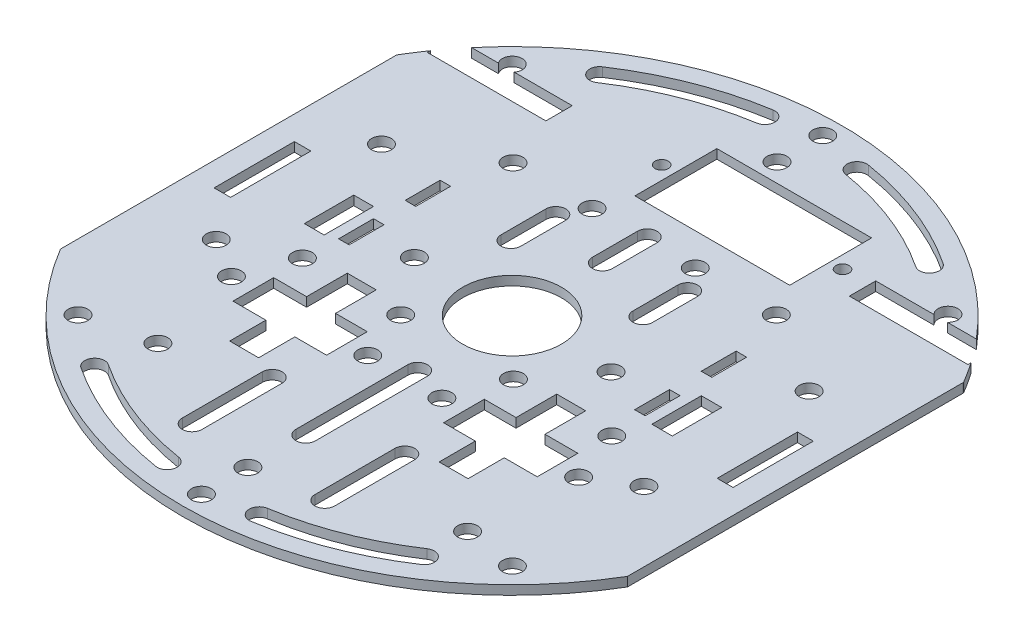
SolidWorks part; units mm, degrees
ref_plane "Plan de face" through (0, 0, 0) normal (0, 0, 1) x (1, 0, 0)
ref_plane "Plan de dessus" through (0, 0, 0) normal (0, 1, 0) x (1, 0, 0)
ref_plane "Plan de droite" through (0, 0, 0) normal (1, 0, 0) x (0, 0, -1)
sketch "Esquisse1" plane through (0, 0, 0) normal (0, 1, 0) x (1, 0, 0)
  line L0 (230, 494) -> (1150, 494) construction
  line L1 (230, 494) -> (1150, 494) construction
  line L2 (1049.7748, 1753.5) -> (2703.7748, 1753.5) construction
  line L3 (35.8344, 116.4831) -> (35.8344, 167.52)
  line L4 (121.9144, 167.4519) -> (121.9144, 116.5513)
  line L5 (88.9323, 158.6153) -> (88.9323, 151.8005) construction
  line L6 (121.9144, 116.5513) -> (121.9144, 116.4831)
  line L7 (55.7773, 128.9032) -> (60.7773, 128.9032)
  line L8 (55.7773, 128.9032) -> (55.7773, 122.7236)
  line L9 (55.7773, 122.7236) -> (60.7773, 122.7236)
  line L10 (60.7773, 122.7236) -> (60.7773, 117.2265)
  line L11 (60.7773, 117.2265) -> (65.1744, 117.2265)
  line L12 (65.1744, 117.2265) -> (65.1744, 122.7236)
  line L13 (65.1744, 122.7236) -> (69.9925, 122.7236)
  line L14 (69.9925, 122.7236) -> (69.9925, 128.9032)
  line L15 (69.9925, 128.9032) -> (65.1744, 128.9032)
  line L16 (65.1744, 128.9032) -> (65.1744, 135.081)
  line L17 (65.1744, 135.081) -> (60.7773, 135.081)
  line L18 (60.7773, 135.081) -> (60.7773, 128.9032)
  line L19 (68.9056, 158.6153) -> (68.9056, 151.8005) construction
  line L20 (70.4056, 158.6153) -> (70.4056, 151.8005)
  line L21 (67.4056, 158.6153) -> (67.4056, 151.8005)
  line L22 (78.7942, 162.6149) -> (78.7942, 155.8001) construction
  line L23 (80.2942, 162.6149) -> (80.2942, 155.8001)
  line L24 (77.2942, 162.6149) -> (77.2942, 155.8001)
  line L25 (68.7987, 115.6611) -> (68.7987, 103.5071) construction
  line L26 (70.2987, 115.6611) -> (70.2987, 103.5071)
  line L27 (67.2987, 115.6611) -> (67.2987, 103.5071)
  line L28 (39.458, 148.3706) -> (41.958, 148.3706)
  line L29 (41.958, 148.3706) -> (41.958, 136.1826)
  line L30 (41.958, 136.1826) -> (39.458, 136.1826)
  line L31 (39.458, 136.1826) -> (39.458, 148.3706)
  line L32 (55.6035, 149.0513) -> (57.2035, 149.0513)
  line L33 (54.0029, 138.3405) -> (51.0029, 138.3405)
  line L34 (54.0029, 138.3405) -> (54.0029, 145.8405)
  line L35 (54.0029, 145.8405) -> (51.0029, 145.8405)
  line L36 (51.0029, 138.3405) -> (51.0029, 145.8405)
  line L37 (55.6035, 138.9387) -> (57.2035, 138.9387)
  line L38 (55.6035, 138.9387) -> (55.6035, 144.2387)
  line L39 (55.6035, 144.2387) -> (57.2035, 144.2387)
  line L40 (57.2035, 138.9387) -> (57.2035, 144.2387)
  line L41 (55.6035, 149.0513) -> (55.6035, 154.3513)
  line L42 (55.6035, 154.3513) -> (57.2035, 154.3513)
  line L43 (57.2035, 149.0513) -> (57.2035, 154.3513)
  line L44 (35.8344, 142.0016) -> (121.9144, 142.0016) construction
  line L45 (78.8744, 142.0016) -> (78.8744, 76.4199) construction
  line L46 (78.9075, 127.6391) -> (78.9075, 110.6391) construction
  line L47 (80.4075, 127.6391) -> (80.4075, 110.6391)
  line L48 (77.4075, 127.6391) -> (77.4075, 110.6391)
  line L49 (35.8344, 162.6149) -> (121.9144, 162.6149) construction
  line L50 (87.4323, 158.6153) -> (87.4323, 151.8005)
  line L51 (90.4323, 158.6153) -> (90.4323, 151.8005)
  line L52 (88.9323, 115.6611) -> (88.9323, 103.5071) construction
  line L53 (87.4323, 115.6611) -> (87.4323, 103.5071)
  line L54 (90.4323, 115.6611) -> (90.4323, 103.5071)
  line L55 (100.5453, 149.0513) -> (100.5453, 154.3513)
  line L56 (102.1454, 154.3551) -> (100.5453, 154.3513)
  line L57 (102.1454, 149.0551) -> (102.1454, 154.3551)
  line L58 (100.5454, 138.9387) -> (100.5454, 144.2387)
  line L59 (102.1454, 144.2387) -> (100.5454, 144.2387)
  line L60 (102.1454, 138.9387) -> (102.1454, 144.2387)
  line L61 (102.1454, 138.9387) -> (100.5454, 138.9387)
  line L62 (106.8661, 138.3405) -> (106.8661, 145.8405)
  line L63 (103.7673, 145.8405) -> (106.8661, 145.8405)
  line L64 (103.7673, 138.3405) -> (103.7673, 145.8405)
  line L65 (103.7673, 138.3405) -> (106.8661, 138.3405)
  line L66 (102.1454, 149.0551) -> (100.5453, 149.0513)
  line L67 (118.245, 136.1826) -> (118.245, 148.3706)
  line L68 (115.8366, 136.1826) -> (118.245, 136.1826)
  line L69 (115.8366, 148.3706) -> (115.8366, 136.1826)
  line L70 (118.245, 148.3706) -> (115.8366, 148.3706)
  line L71 (96.9716, 135.081) -> (96.9716, 128.9032)
  line L72 (92.5745, 135.081) -> (96.9716, 135.081)
  line L73 (92.5745, 128.9032) -> (92.5745, 135.081)
  line L74 (87.7564, 128.9032) -> (92.5745, 128.9032)
  line L75 (87.7564, 122.7236) -> (87.7564, 128.9032)
  line L76 (92.5745, 122.7236) -> (87.7564, 122.7236)
  line L77 (92.5745, 117.2265) -> (92.5745, 122.7236)
  line L78 (96.9716, 117.2265) -> (92.5745, 117.2265)
  line L79 (96.9716, 122.7236) -> (96.9716, 117.2265)
  line L80 (101.9716, 122.7236) -> (96.9716, 122.7236)
  line L81 (101.9716, 128.9032) -> (101.9716, 122.7236)
  line L82 (101.9716, 128.9032) -> (96.9716, 128.9032)
  line L84 (72.4514, 167.0754) -> (95.9525, 167.0754)
  line L85 (72.4514, 167.0754) -> (72.4514, 179.5181)
  line L86 (72.4514, 179.5181) -> (95.9525, 179.5181)
  line L87 (95.9525, 167.0754) -> (95.9525, 179.5181)
  arc A1 (35.8344, 116.4831) -> (121.9144, 116.4831) centre (78.8744, 142.0016) ccw
  circle A2 centre (78.8744, 142.0016) radius 7.5
  arc A3 (121.8796, 167.5788) -> (35.8344, 167.52) centre (78.8744, 142.0016) ccw
  circle A4 centre (55.6386, 111.4684) radius 1.5
  circle A5 centre (52.4216, 125.8435) radius 1.5
  circle A6 centre (46.4093, 129.5605) radius 1.5
  circle A7 centre (45.8266, 109.1504) radius 1.5
  circle A9 centre (55.394, 133.6521) radius 1.5
  circle A10 centre (63.822, 142.2216) radius 1.5
  circle A11 centre (70.318, 133.6521) radius 1.5
  circle A12 centre (73.1582, 125.8134) radius 1.5
  circle A14 centre (78.7794, 94.9342) radius 1.5
  circle A15 centre (58.8593, 162.1633) radius 1.5
  circle A16 centre (78.7794, 101.9917) radius 1.5
  circle A17 centre (45.8266, 175.0806) radius 1.5
  circle A18 centre (78.7794, 182.3243) radius 1.5
  circle A19 centre (46.4093, 154.6416) radius 1.5
  circle A20 centre (78.7794, 189.2658) radius 1.5
  circle A21 centre (70.8644, 162.1633) radius 1.5
  arc A24 (70.4056, 158.6153) -> (67.4056, 158.6153) centre (68.9056, 158.6153) ccw
  arc A25 (67.4056, 151.8005) -> (70.4056, 151.8005) centre (68.9056, 151.8005) ccw
  arc A26 (80.2942, 162.6149) -> (77.2942, 162.6149) centre (78.7942, 162.6149) ccw
  arc A27 (77.2942, 155.8001) -> (80.2942, 155.8001) centre (78.7942, 155.8001) ccw
  arc A30 (70.2987, 115.6611) -> (67.2987, 115.6611) centre (68.7987, 115.6611) ccw
  arc A31 (67.2987, 103.5071) -> (70.2987, 103.5071) centre (68.7987, 103.5071) ccw
  arc A35 (53.8408, 103.6654) -> (71.8854, 96.6187) centre (79.1758, 141.9141) ccw construction
  arc A36 (53.0125, 102.4148) -> (71.647, 95.1377) centre (79.1758, 141.9141) ccw
  arc A37 (54.6692, 104.9159) -> (72.1238, 98.0996) centre (79.1758, 141.9141) ccw
  arc A38 (54.6692, 104.9159) -> (53.0125, 102.4148) centre (53.8408, 103.6654) ccw
  arc A39 (71.647, 95.1377) -> (72.1238, 98.0996) centre (71.8854, 96.6187) ccw
  circle A40 centre (78.9075, 110.6391) radius 1.5
  circle A41 centre (78.9075, 127.6391) radius 1.5
  arc A42 (80.4075, 127.6391) -> (77.4075, 127.6391) centre (78.9075, 127.6391) ccw
  arc A43 (77.4075, 110.6391) -> (80.4075, 110.6391) centre (78.9075, 110.6391) ccw
  arc A44 (53.8408, 180.3378) -> (71.8854, 187.3845) centre (79.1758, 142.0891) cw construction
  arc A45 (53.0125, 181.5883) -> (71.647, 188.8654) centre (79.1758, 142.0891) cw
  arc A46 (54.6692, 179.0872) -> (72.1238, 185.9035) centre (79.1758, 142.0891) cw
  arc A47 (54.6692, 179.0872) -> (53.0125, 181.5883) centre (53.8408, 180.3378) cw
  arc A48 (71.647, 188.8654) -> (72.1238, 185.9035) centre (71.8854, 187.3845) cw
  circle A49 centre (70.4056, 173.1853) radius 1
  arc A50 (87.4323, 158.6153) -> (90.4323, 158.6153) centre (88.9323, 158.6153) cw
  arc A51 (90.4323, 151.8005) -> (87.4323, 151.8005) centre (88.9323, 151.8005) cw
  arc A52 (87.4323, 115.6611) -> (90.4323, 115.6611) centre (88.9323, 115.6611) cw
  arc A53 (90.4323, 103.5071) -> (87.4323, 103.5071) centre (88.9323, 103.5071) cw
  arc A54 (103.908, 103.6654) -> (85.8635, 96.6187) centre (78.573, 141.9141) cw construction
  arc A55 (104.7364, 102.4148) -> (86.1018, 95.1377) centre (78.573, 141.9141) cw
  arc A56 (103.0797, 104.9159) -> (85.6251, 98.0996) centre (78.573, 141.9141) cw
  arc A57 (103.0797, 104.9159) -> (104.7364, 102.4148) centre (103.908, 103.6654) cw
  arc A58 (86.1018, 95.1377) -> (85.6251, 98.0996) centre (85.8635, 96.6187) cw
  arc A59 (103.908, 180.3378) -> (85.8635, 187.3845) centre (78.573, 142.0891) ccw construction
  arc A60 (104.7364, 181.5883) -> (86.1018, 188.8654) centre (78.573, 142.0891) ccw
  arc A61 (103.0797, 179.0872) -> (85.6251, 185.9035) centre (78.573, 142.0891) ccw
  arc A62 (103.0797, 179.0872) -> (104.7364, 181.5883) centre (103.908, 180.3378) ccw
  arc A63 (86.1018, 188.8654) -> (85.6251, 185.9035) centre (85.8635, 187.3845) ccw
  circle A64 centre (97.8643, 173.1853) radius 1
  circle A66 centre (86.5331, 162.1633) radius 1.5
  circle A67 centre (111.3396, 154.6416) radius 1.5
  circle A68 centre (111.7891, 175.2768) radius 1.5
  circle A69 centre (98.8379, 162.1633) radius 1.5
  circle A70 centre (84.4104, 125.8134) radius 1.5
  circle A71 centre (87.3272, 133.7572) radius 1.5
  circle A72 centre (93.7831, 142.1236) radius 1.5
  circle A73 centre (102.2561, 133.7572) radius 1.5
  circle A74 centre (105.1676, 125.8134) radius 1.5
  circle A75 centre (111.8296, 109.1035) radius 1.5
  circle A76 centre (111.3396, 129.5605) radius 1.5
  circle A78 centre (103.8661, 110.2588) radius 1.5
  arc A79 (121.8796, 167.5788) -> (121.9144, 167.4519) centre (121.6662, 167.4519) cw
  point P32 (68.9056, 155.2079)
  point P38 (55.6386, 111.4684)
  point P42 (78.7942, 159.2075)
  point P63 (68.7987, 109.5841)
  point P106 (78.9075, 119.1391)
  point P110 (62.487, 99.1788)
  point P129 (62.487, 184.8244)
  point P138 (35.8344, 167.52)
  point P139 (88.9323, 155.2079)
  point P146 (88.9323, 109.5841)
  point P154 (95.2619, 99.1788)
  point P162 (95.2619, 184.8244)
  point P225 (121.9144, 167.52)
  point P226 (102.1103, 111.4684)
  dimension "D3" = 15
  dimension "D5" = 3
  dimension "D6" = 1.5
  dimension "D7" = 1.5
  dimension "D14" = 3
  dimension "D17" = 2
  dimension "D18" = 3
  dimension "D19" = 3
  dimension "D20" = 3
  dimension "D21" = 3
  dimension "D22" = 3
  dimension "D23" = 3
  dimension "D24" = 3
  dimension "D25" = 3
  dimension "D26" = 3
  dimension "D27" = 3
  dimension "D29" = 3
  dimension "D33" = 1.5
  dimension "D35" = 3
  dimension "D2" = 51.0369
  dimension "D4" = 5
  dimension "D8" = 2.5
  dimension "D9" = 12.1879
  dimension "D10" = 3
  dimension "D11" = 7.5
  dimension "D12" = 1.6
  dimension "D13" = 5.3
  dimension "D15" = 3
  dimension "D16" = 17
  dimension "D28" = 12.1541
  dimension "D30" = 6.8148
  dimension "D31" = 43.04
  dimension "D32" = 43.04
  dimension "D34" = 6.8148
  dimension "D36" = 12.1541
  dimension "D37" = 1.6
  dimension "D38" = 5.3
extrude "Boss.-Extru.1" add sketch "Esquisse1" along normal blind 1.4 contours A79 A3 L3 A1 L6 L4 A76 A74 A72 A70 A68 A66 A55 A58 A56 A57 L54 A53 L53 A52 L51 A51 L50 A50 A45 A48 A46 A47 L57 L66 L55 L56 L60 L61 L58 L59 L33 L36 region at (37.1544, 0, -142.0016)
sketch "Esquisse2" plane through (0, 0, 0) normal (0, -1, 0) x (-1, 0, 0)
  line L0 (-121.9144, 167.4519) -> (-121.9144, 116.4831) construction
  line L1 (-101.9144, 174.1788) -> (-119.9144, 174.1788)
  line L2 (-101.9144, 174.1788) -> (-101.9144, 170.1788)
  line L3 (-101.9144, 170.1788) -> (-119.9144, 170.1788)
  line L4 (-119.9144, 174.1788) -> (-119.9144, 170.1788)
  line L5 (-35.8344, 116.4831) -> (-35.8344, 167.52) construction
  line L6 (-37.8344, 174.1788) -> (-55.8344, 174.1788)
  line L7 (-37.8344, 174.1788) -> (-37.8344, 170.1788)
  line L8 (-37.8344, 170.1788) -> (-55.8344, 170.1788)
  line L9 (-55.8344, 174.1788) -> (-55.8344, 170.1788)
  dimension "D1" = 2
  dimension "D2" = 4
  dimension "D3" = 18
  dimension "D5" = 2
  dimension "D6" = 6.6
  dimension "D8" = 18
extrude "Enlèv. mat.-Extru.1" cut sketch "Esquisse2" against normal blind 10
